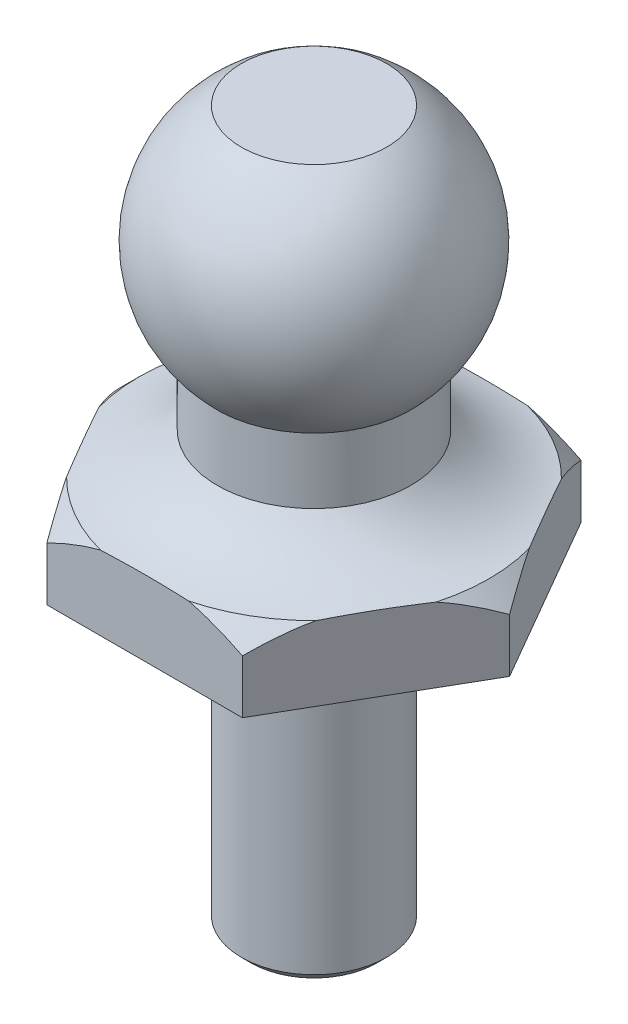
SolidWorks part; units mm, degrees
ref_plane "Front" through (0, 0, 0) normal (0, 0, 1) x (1, 0, 0)
ref_plane "Top" through (0, 0, 0) normal (0, 1, 0) x (1, 0, 0)
ref_plane "Right" through (0, 0, 0) normal (1, 0, 0) x (0, 0, -1)
sketch "Esquisse1" plane through (0, 0, 0) normal (0, 0, 1) x (1, 0, 0)
  line L0 (0, -9.2102) -> (0, 11.189) construction
  line L1 (0, -6.5) -> (-1.5, -6.5)
  line L2 (-1.5, -6.5) -> (-1.5, 0)
  line L3 (-1.5, 0) -> (-4.05, 0)
  line L4 (-4.05, 0) -> (-4.05, 1.5)
  line L5 (-2, 2.3963) -> (-2, 3.7463)
  line L6 (0, 8.2) -> (0, -6.5)
  line L7 (-1.5, 8.2) -> (0, 8.2)
  arc A0 (-1.5, 8.2) -> (-2, 3.7463) centre (0, 5.7767) ccw
  arc A1 (-4.05, 1.5) -> (-2, 2.3963) centre (-4.05, 4.2925) ccw
  point P14 (-0.75, 8.2)
  point P22 (0, 5.7767)
  dimension "D1" = 2.85
  dimension "D2" = 8.2
  dimension "D3" = 3
  dimension "D4" = 6.5
  dimension "D5" = 8.1
  dimension "D6" = 1.5
  dimension "D7" = 4
  dimension "D8" = 1.35
  dimension "D9" = 3
revolve "Révolution1" add sketch "Esquisse1" angle 360 about L0
chamfer "Chanfrein1" distance 0.4 angle 45 1 edges at (0, 1.5, -4.05)
sketch "Esquisse2" plane through (0, 0, 0) normal (0, -1, 0) x (1, 0, 0)
  line L1 (2.0207, 3.5) -> (-2.0207, 3.5)
  line L2 (-2.0207, 3.5) -> (-4.0415, 0)
  line L3 (-4.0415, 0) -> (-2.0207, -3.5)
  line L4 (-2.0207, -3.5) -> (2.0207, -3.5)
  line L5 (2.0207, -3.5) -> (4.0415, 0)
  line L6 (4.0415, 0) -> (2.0207, 3.5)
  circle A0 centre (0, 0) radius 3.5 construction
  dimension "D1" = 7
extrude "Enlèv. mat.-Extru.1" cut sketch "Esquisse2" against normal through all flip side to cut
chamfer "Chanfrein2" distance 0.2 angle 45 1 edges at (0, -6.5, -1.5)
fillet "Congé2" radius 0.1 1 edges at (0, 0, -1.5)
